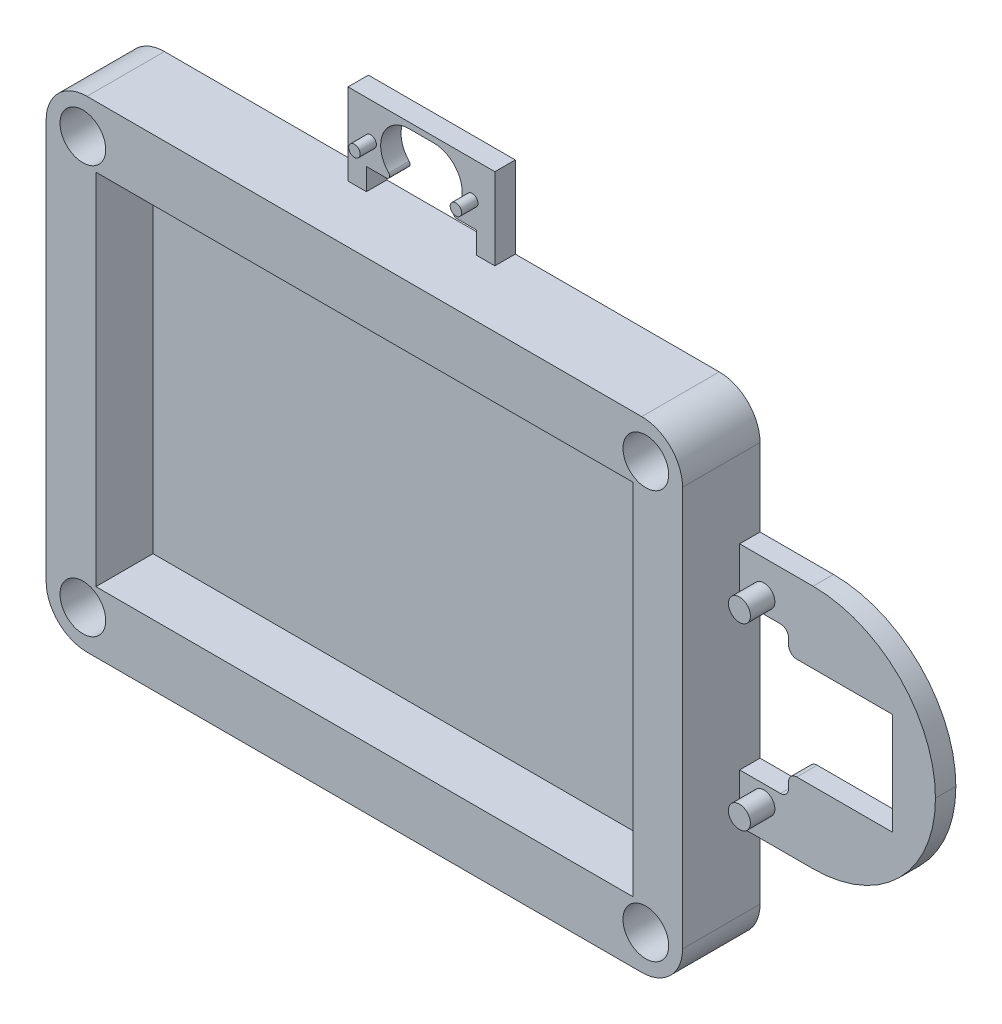
SolidWorks part; units mm, degrees
ref_plane "Front Plane" through (0, 0, 0) normal (1, 0, 0) x (0, 1, 0)
ref_plane "Top Plane" through (0, 0, 0) normal (0, 0, 1) x (0, 1, 0)
ref_plane "Right Plane" through (0, 0, 0) normal (0, 1, 0) x (-1, 0, 0)
sketch "Sketch1" plane through (0, 0, 0) normal (0, 0, 1) x (0, 1, 0)
  line L1 (-27.94, -41.783) -> (27.94, -41.783)
  line L2 (-27.94, -41.783) -> (-27.94, 41.783)
  line L3 (-27.94, 41.783) -> (27.94, 41.783)
  line L4 (27.94, -41.783) -> (27.94, 41.783)
  line L5 (-27.94, -41.783) -> (27.94, 41.783) construction
  line L6 (-27.94, 41.783) -> (27.94, -41.783) construction
  point P0 (0, 0)
  dimension "D1" = 55.88
  dimension "D2" = 83.566
extrude "Boss-Extrude1" add sketch "Sketch1" along normal blind 3.175
sketch "Sketch2" plane through (0, 0, 0) normal (0, 0, 1) x (0, 1, 0)
  line L8 (37.465, -51.308) -> (37.465, 51.308)
  line L9 (37.465, 51.308) -> (-37.465, 51.308)
  line L10 (-37.465, 51.308) -> (-37.465, -51.308)
  line L11 (-37.465, -51.308) -> (37.465, -51.308)
  line L12 (37.465, -51.308) -> (37.465, 51.308)
  line L13 (37.465, 51.308) -> (-37.465, 51.308)
  line L14 (-37.465, 51.308) -> (-37.465, -51.308)
  line L15 (-37.465, -51.308) -> (37.465, -51.308)
  line L16 (27.94, -41.783) -> (27.94, 41.783)
  line L17 (27.94, 41.783) -> (-27.94, 41.783)
  line L18 (-27.94, 41.783) -> (-27.94, -41.783)
  line L19 (-27.94, -41.783) -> (27.94, -41.783)
  line L20 (27.94, -41.783) -> (27.94, 41.783)
  line L21 (27.94, 41.783) -> (-27.94, 41.783)
  line L22 (-27.94, 41.783) -> (-27.94, -41.783)
  line L23 (-27.94, -41.783) -> (27.94, -41.783)
  dimension "D1" = 9.525
  dimension "D2" = 0
extrude "Boss-Extrude2" add sketch "Sketch2" along normal offset from surface (12.065 mm away) 8.89 contours L14 L15 L12 L13 L23 L22 L21 L20 region at (50.0374, 0, 0) up to face at (0, 0, 3.175) offset beyond the face yes
sketch "Sketch3" plane through (0, 0, 12.065) normal (0, 0, 1) x (1, 0, 0)
  line L0 (-43.815, 31.75) -> (43.815, 31.75) construction
  line L1 (-43.815, 31.75) -> (-43.815, -31.75) construction
  circle A0 centre (-43.815, 31.75) radius 3.556
  circle A1 centre (43.815, 31.75) radius 3.556
  circle A2 centre (43.815, -31.75) radius 3.556
  circle A3 centre (-43.815, -31.75) radius 3.556
  point P8 (0, 31.75)
  point P9 (-43.815, 0)
  dimension "D1" = 7.112
  dimension "D2" = 87.63
  dimension "D3" = 63.5
extrude "Cut-Extrude1" cut sketch "Sketch3" against normal through all both and the other way through all
sketch "Sketch4" plane through (0, 0, 12.065) normal (0, 0, 1) x (1, 0, 0)
  line L0 (-51.308, -37.465) -> (51.308, -37.465) construction
  line L1 (-51.308, 37.465) -> (-49.53, 37.465)
  line L2 (-51.308, 37.465) -> (-51.308, -37.465)
  line L3 (-51.308, -37.465) -> (-49.53, -37.465)
  line L4 (-49.53, 37.465) -> (-49.53, -37.465)
  line L5 (-47.371, 31.75) -> (-49.53, 31.75) construction
  line L6 (51.308, 37.465) -> (49.53, 37.465)
  line L7 (51.308, 37.465) -> (51.308, -37.465)
  line L8 (51.308, -37.465) -> (49.53, -37.465)
  line L9 (49.53, 37.465) -> (49.53, -37.465)
  line L10 (-43.815, 35.306) -> (-43.815, 37.465) construction
  line L11 (51.308, 37.465) -> (-51.308, 37.465) construction
  line L12 (-47.371, 31.75) -> (-43.815, 31.75) construction
  line L13 (-43.815, 35.306) -> (-43.815, 31.75) construction
  circle A0 centre (-43.815, 31.75) radius 3.556 construction
extrude "Cut-Extrude2" cut sketch "Sketch4" against normal through all both and the other way through all
fillet "Fillet1" radius 6.35 4 edges at (-49.53, -37.465, 6.0325) (-49.53, 37.465, 6.0325) (49.53, 37.465, 6.0325) (49.53, -37.465, 6.0325)
fillet "Fillet2" radius 0.508 4 edges at (-40.259, 31.75, 0) (47.371, 31.75, 0) (47.371, -31.75, 0) (-40.259, -31.75, 0)
sketch "Sketch5" plane through (49.53, 0, 0) normal (1, 0, 0) x (0, 1, 0)
  line L1 (-19.05, 3.175) -> (19.05, 3.175)
  line L2 (-19.05, 3.175) -> (-19.05, 0)
  line L3 (-19.05, 0) -> (19.05, 0)
  line L4 (19.05, 3.175) -> (19.05, 0)
  point P4 (0, 0)
  dimension "D1" = 3.175
  dimension "D2" = 38.1
extrude "Boss-Extrude3" add sketch "Sketch5" along normal blind 30.48
sketch "Sketch6" plane through (0, 0, 3.175) normal (0, 0, 1) x (1, 0, 0)
  line L0 (80.01, 19.05) -> (80.01, -19.05) construction
  line L1 (49.53, 11.43) -> (57.15, 11.43)
  line L2 (49.53, 11.43) -> (49.53, -11.43)
  line L3 (49.53, -11.43) -> (57.15, -11.43)
  line L4 (57.15, 11.43) -> (57.15, -11.43)
  line L5 (49.53, -31.115) -> (49.53, 31.115) construction
  point P8 (49.53, 0)
  point P9 (80.01, 0)
  dimension "D1" = 22.86
  dimension "D2" = 7.62
extrude "Cut-Extrude3" cut sketch "Sketch6" against normal through all both and the other way through all
sketch "Sketch7" plane through (0, 0, 3.175) normal (0, 0, 1) x (1, 0, 0)
  line L0 (53.3019, 13.9573) -> (53.3019, -13.9573) construction
  line L1 (49.53, 0) -> (80.01, 0) construction
  line L2 (49.53, -31.115) -> (49.53, 31.115) construction
  line L3 (80.01, 19.05) -> (80.01, -19.05) construction
  line L4 (49.53, 19.05) -> (49.53, 11.43) construction
  circle A0 centre (53.3019, 13.9573) radius 1.7145
  circle A1 centre (53.3019, -13.9573) radius 1.7145
  point P10 (53.3019, 0)
  dimension "D1" = 3.429
  dimension "D2" = 24.4856
  dimension "D3" = 2.0574
extrude "Boss-Extrude4" add sketch "Sketch7" along normal blind 3.81
sketch "Sketch8" plane through (0, 0, 3.175) normal (0, 0, 1) x (1, 0, 0)
  line L0 (80.01, 19.05) -> (80.01, -19.05) construction
  line L1 (80.01, 7.9375) -> (57.15, 7.9375)
  line L2 (80.01, 7.9375) -> (80.01, -7.9375)
  line L3 (80.01, -7.9375) -> (57.15, -7.9375)
  line L4 (57.15, 7.9375) -> (57.15, -7.9375)
  line L5 (57.15, 11.43) -> (57.15, -11.43) construction
  point P6 (57.15, 0)
  dimension "D1" = 15.875
extrude "Cut-Extrude4" cut sketch "Sketch8" against normal through all both and the other way through all
sketch "Sketch9" plane through (0, 0, 3.175) normal (0, 0, 1) x (1, 0, 0)
  line L0 (80.01, -7.9375) -> (57.15, -7.9375) construction
  line L1 (80.01, 7.9375) -> (73.3171, 7.9375)
  line L2 (80.01, 7.9375) -> (80.01, -7.9375)
  line L3 (80.01, -7.9375) -> (73.3171, -7.9375)
  line L4 (73.3171, 7.9375) -> (73.3171, -7.9375)
  line L5 (49.53, -31.115) -> (49.53, 31.115) construction
  dimension "D1" = 23.7871
extrude "Boss-Extrude5" add sketch "Sketch9" against normal up to surface (3.175 mm away) up to face at (-47.879, 31.75, 0)
fillet "Fillet3" radius 19.05 2 edges at (80.01, -19.05, 1.5875) (80.01, 19.05, 1.5875)
fillet "Fillet5" radius 1.27 4 edges at (57.15, 7.9375, 1.5875) (57.15, -7.9375, 1.5875) (57.15, -11.43, 1.5875) (57.15, 11.43, 1.5875)
sketch "Sketch14" plane through (0, 37.465, 0) normal (0, 1, 0) x (-1, 0, 0)
  line L0 (-43.18, 0) -> (43.18, 0) construction
  line L1 (-11.43, 0) -> (11.43, 0)
  line L2 (-11.43, 0) -> (-11.43, 3.175)
  line L3 (-11.43, 3.175) -> (11.43, 3.175)
  line L4 (11.43, 0) -> (11.43, 3.175)
  line L5 (-60.96, 3.175) -> (-80.01, 3.175) construction
  point P8 (0, 0)
  dimension "D1" = 22.86
extrude "Boss-Extrude8" add sketch "Sketch14" along normal blind 12.7 contours L3 L4 L1 L2
sketch "Sketch15" plane through (0, 0, 3.175) normal (0, 0, 1) x (1, 0, 0)
  line L0 (-1.905, 44.831) -> (1.905, 44.831) construction
  line L1 (-1.905, 49.276) -> (1.905, 49.276)
  line L2 (-1.905, 40.386) -> (1.905, 40.386)
  line L3 (11.43, 37.465) -> (-11.43, 37.465) construction
  arc A0 (-1.905, 49.276) -> (-1.905, 40.386) centre (-1.905, 44.831) ccw
  arc A1 (1.905, 40.386) -> (1.905, 49.276) centre (1.905, 44.831) ccw
  point P2 (0, 44.831)
  dimension "D1" = 4.445
  dimension "D2" = 11.811
  dimension "D3" = 3.81
extrude "Cut-Extrude7" cut sketch "Sketch15" against normal through all both and the other way through all
sketch "Sketch16" plane through (0, 0, 3.175) normal (0, 0, 1) x (1, 0, 0)
  line L0 (11.43, 37.465) -> (-11.43, 37.465) construction
  line L1 (-8.5654, 40.8686) -> (8.5654, 40.8686)
  line L2 (-8.5654, 40.8686) -> (-8.5654, 37.465)
  line L3 (-8.5654, 37.465) -> (8.5654, 37.465)
  line L4 (8.5654, 40.8686) -> (8.5654, 37.465)
  point P4 (0, 37.465)
  dimension "D1" = 3.4036
extrude "Cut-Extrude8" cut sketch "Sketch16" against normal through all both and the other way through all
fillet "Fillet8" radius 0.508 2 edges at (-3.9193, 40.8686, 1.5875) (3.9193, 40.8686, 1.5875)
sketch "Sketch17" plane through (0, 0, 3.175) normal (0, 0, 1) x (1, 0, 0)
  line L0 (-7.8994, 44.577) -> (7.8994, 44.577) construction
  line L1 (11.43, 37.465) -> (8.5654, 37.465) construction
  circle A0 centre (-7.8994, 44.577) radius 0.889
  circle A1 centre (7.8994, 44.577) radius 0.889
  point P4 (0, 44.577)
  dimension "D1" = 1.778
  dimension "D2" = 7.112
  dimension "D3" = 15.7988
extrude "Boss-Extrude9" add sketch "Sketch17" along normal blind 2.54
